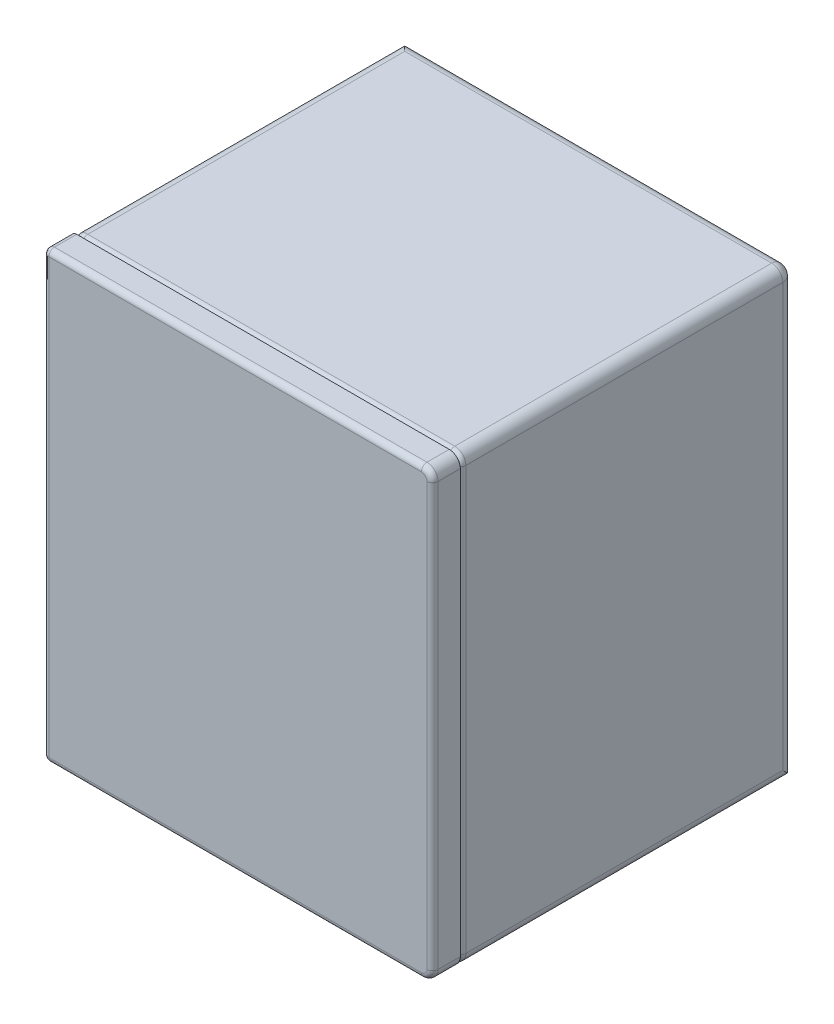
SolidWorks part; units mm, degrees
ref_plane "Front Plane" through (0, 0, 0) normal (0, 0, 1) x (1, 0, 0)
ref_plane "Top Plane" through (0, 0, 0) normal (0, 1, 0) x (1, 0, 0)
ref_plane "Right Plane" through (0, 0, 0) normal (1, 0, 0) x (0, 0, -1)
sketch "Sketch2" plane through (0, 0, 0) normal (0, 1, 0) x (1, 0, 0)
  line L1 (0, 0) -> (700, 0)
  line L2 (0, 0) -> (0, 600)
  line L3 (0, 600) -> (700, 600)
  line L4 (700, 0) -> (700, 600)
extrude "Boss-Extrude1" add sketch "Sketch2" along normal blind 800
ref_plane "Plane1" through (0, 0, 0) normal (0, 0, 1) x (1, 0, 0)
fillet "Fillet1" radius 10 3 edges at (350, 0, 0) (700, 400, 0) (350, 800, 0)
fillet "Fillet2" radius 20 11 edges at (697.0711, 797.0711, -2.9289) (697.0711, 2.9289, -2.9289) (0, 0, -305) (0, 2.9289, -2.9289) (0, 400, 0) (0, 797.0711, -2.9289) (350, 800, -600) (0, 800, -305) (700, 400, -600) (700, 0, -305) (700, 800, -305)
sketch "Sketch3" plane through (0, 0, 0) normal (0, 0, 1) x (1, 0, 0)
  line L1 (0, 800) -> (700, 800)
  line L2 (0, 800) -> (0, 0)
  line L3 (0, 0) -> (700, 0)
  line L4 (700, 800) -> (700, 0)
extrude "Boss-Extrude2" add sketch "Sketch3" along normal blind 50 separate body
fillet "Fillet3" radius 10 4 edges at (350, 800, 50) (700, 400, 50) (350, 0, 50) (0, 400, 50)
fillet "Fillet4" radius 10 4 edges at (2.9289, 2.9289, 47.0711) (2.9289, 797.0711, 47.0711) (0, 0, 20) (0, 800, 20)
fillet "Fillet5" radius 20 4 edges at (697.0711, 797.0711, 47.0711) (697.0711, 2.9289, 47.0711) (700, 0, 20) (700, 800, 20)
